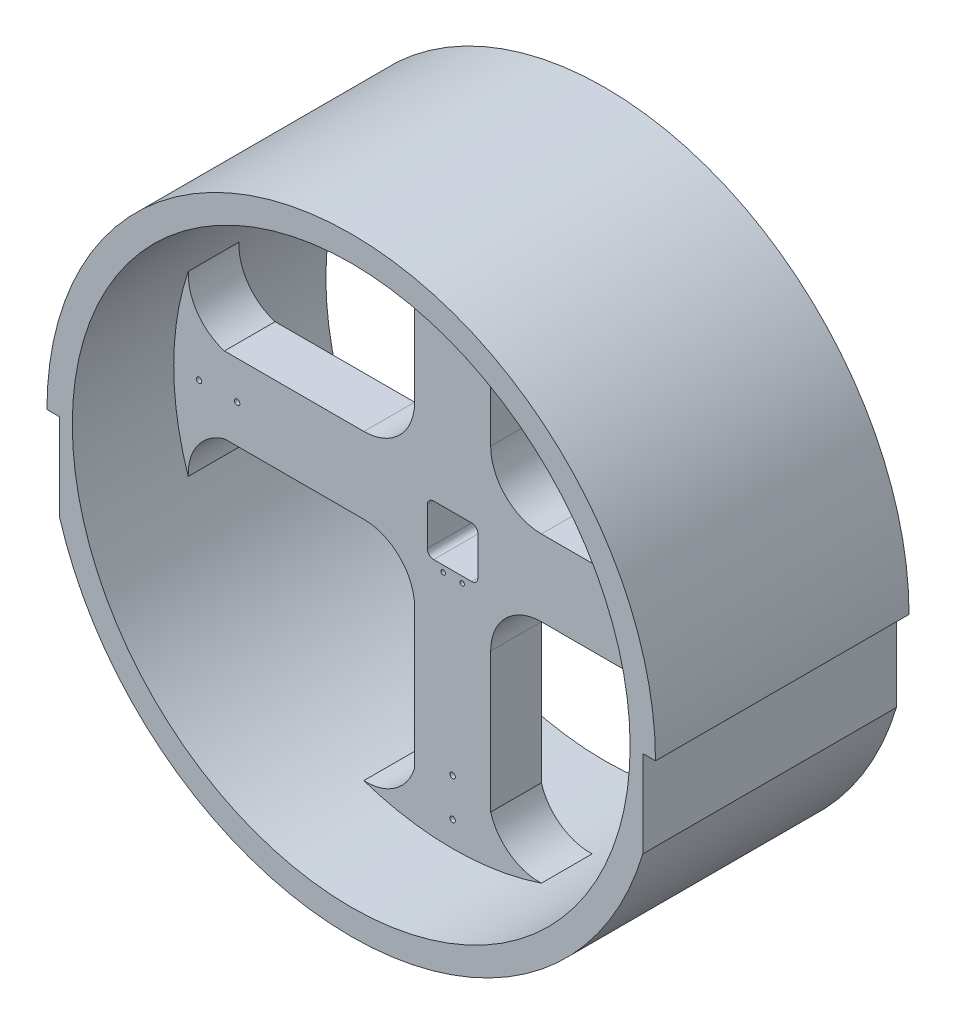
SolidWorks part; units mm, degrees
material "6061 Alloy"
ref_plane "Front Plane" through (0, 0, 0) normal (0, 0, 1) x (1, 0, 0)
ref_plane "Top Plane" through (0, 0, 0) normal (0, 1, 0) x (1, 0, 0)
ref_plane "Right Plane" through (0, 0, 0) normal (1, 0, 0) x (0, 0, -1)
sketch "Sketch1" plane through (0, 0, 0) normal (0, 0, 1) x (1, 0, 0)
  circle A0 centre (0, 0) radius 152.4
  circle A1 centre (0, 0) radius 139.7
  dimension "D1" = 304.8
  dimension "D2" = 279.4
extrude "Boss-Extrude1" add sketch "Sketch1" along normal mid plane 127
sketch "Sketch2" plane through (0, 0, 0) normal (0, 0, 1) x (1, 0, 0)
  line L0 (-114.3, 19.05) -> (-138.7192, 19.05)
  line L1 (-147.1918, -19.05) -> (147.1918, -19.05)
  line L2 (-147.1918, -19.05) -> (-147.1918, 19.05)
  line L3 (-147.1918, 19.05) -> (147.1918, 19.05)
  line L4 (147.1918, -19.05) -> (147.1918, 19.05)
  line L5 (-147.1918, -19.05) -> (147.1918, 19.05) construction
  line L6 (-147.1918, 19.05) -> (147.1918, -19.05) construction
  line L7 (19.05, -143.9568) -> (-19.05, -143.9568)
  line L8 (19.05, -143.9568) -> (19.05, 143.9568)
  line L9 (19.05, 143.9568) -> (-19.05, 143.9568)
  line L10 (-19.05, -143.9568) -> (-19.05, 143.9568)
  line L11 (19.05, -143.9568) -> (-19.05, 143.9568) construction
  line L12 (19.05, 143.9568) -> (-19.05, -143.9568) construction
  line L15 (-44.45, 19.05) -> (-19.05, 19.05)
  line L16 (-19.05, 44.45) -> (-19.05, 19.05)
  line L17 (-132.4254, 44.4927) -> (-143.3503, 19.05)
  line L18 (-143.3503, 19.05) -> (-138.7192, 19.05)
  line L19 (-138.7192, 19.05) -> (-143.3503, 19.05)
  line L20 (-19.05, 114.3) -> (-19.05, 143.9568)
  line L21 (-44.45, 132.4398) -> (-19.05, 143.9568)
  line L22 (44.45, 19.05) -> (19.05, 19.05)
  line L23 (19.05, 44.45) -> (19.05, 19.05)
  line L24 (19.05, 143.3503) -> (19.05, 138.7192)
  line L25 (19.05, 114.3) -> (19.05, 138.7192)
  line L26 (44.4927, 132.4254) -> (19.05, 143.3503)
  line L27 (114.3, 19.05) -> (143.9568, 19.05)
  line L28 (132.4398, 44.45) -> (143.9568, 19.05)
  line L29 (19.05, -44.45) -> (19.05, -19.05)
  line L30 (44.45, -19.05) -> (19.05, -19.05)
  line L31 (143.3503, -19.05) -> (138.7192, -19.05)
  line L32 (114.3, -19.05) -> (138.7192, -19.05)
  line L33 (132.4254, -44.4927) -> (143.3503, -19.05)
  line L34 (19.05, -114.3) -> (19.05, -143.9568)
  line L35 (44.45, -132.4398) -> (19.05, -143.9568)
  line L36 (-44.45, -19.05) -> (-19.05, -19.05)
  line L37 (-19.05, -44.45) -> (-19.05, -19.05)
  line L38 (-19.05, -143.3503) -> (-19.05, -138.7192)
  line L39 (-19.05, -114.3) -> (-19.05, -138.7192)
  line L40 (-44.4927, -132.4254) -> (-19.05, -143.3503)
  line L41 (-114.3, -19.05) -> (-143.9568, -19.05)
  line L42 (-132.4398, -44.45) -> (-143.9568, -19.05)
  arc A1 (-44.45, 19.05) -> (-19.05, 44.45) centre (-44.45, 44.45) ccw
  arc A2 (-114.3, 19.05) -> (-132.4254, 44.4927) centre (-107.0492, 43.3931) cw
  circle A3 centre (0, 0) radius 139.7 construction
  arc A5 (-19.05, 114.3) -> (-44.45, 132.4398) centre (-43.3968, 107.0616) ccw
  arc A6 (19.05, 44.45) -> (44.45, 19.05) centre (44.45, 44.45) ccw
  arc A7 (19.05, 114.3) -> (44.4927, 132.4254) centre (43.3931, 107.0492) cw
  arc A8 (114.3, 19.05) -> (132.4398, 44.45) centre (107.0616, 43.3968) ccw
  arc A9 (44.45, -19.05) -> (19.05, -44.45) centre (44.45, -44.45) ccw
  arc A10 (114.3, -19.05) -> (132.4254, -44.4927) centre (107.0492, -43.3931) cw
  arc A11 (19.05, -114.3) -> (44.45, -132.4398) centre (43.3968, -107.0616) ccw
  arc A12 (-19.05, -44.45) -> (-44.45, -19.05) centre (-44.45, -44.45) ccw
  arc A13 (-19.05, -114.3) -> (-44.4927, -132.4254) centre (-43.3931, -107.0492) cw
  arc A14 (-114.3, -19.05) -> (-132.4398, -44.45) centre (-107.0616, -43.3968) ccw
  point P0 (0, 0)
  point P6 (0, 0)
  point P67 (0, 0)
  dimension "D3" = 25.4
  dimension "D5" = 25.4
  dimension "D1" = 38.1
  dimension "D2" = 38.1
  dimension "D4" = 114.3
  dimension "D6" = 114.3
  dimension "D7" = 4
extrude "Boss-Extrude2" add sketch "Sketch2" along normal mid plane 25.4 contours L1 L10 L3 L2 | L10 L1 L8 L3 | L10 L3 L8 L9 | L8 L1 L4 L3 | L10 L7 L8 L1 | A14 L1 L42 | L10 A13 L40 | A11 L8 L35 | A9 L1 L8 | L1 A10 L33 | A8 L3 L28 | L8 A7 L26 | A5 L10 L21 | L0 A2 L17 L3 | A1 L3 L10 | A6 L8 L3 | A12 L10 L1 region at (-83.1209, 0, 0) region at (-132.2215, 26.1932, 0) region at (-24.7235, 24.7235, 0) region at (0, 81.5034, 0) region at (0, 0, 0) region at (24.7235, 24.7235, 0) region at (83.1209, 0, 0) region at (-24.7235, -24.7235, 0) region at (0, -81.5034, 0) region at (-26.2233, 132.4495, 0) region at (24.7235, -24.7235, 0) region at (-132.4495, -26.2233, 0) region at (132.4495, 26.2233, 0) region at (26.1932, 132.2215, 0) region at (-26.1932, -132.2215, 0) region at (132.2215, -26.1932, 0) region at (26.2233, -132.4495, 0)
sketch "Sketch4" plane through (0, 0, 0) normal (0, 0, 1) x (1, 0, 0)
  line L0 (-12.7, -19.05) -> (-12.7, 6.35)
  line L5 (-12.7, -19.05) -> (12.7, -19.05)
  line L6 (-12.7, 6.35) -> (12.7, 6.35)
  line L7 (12.7, -19.05) -> (12.7, 6.35)
  line L8 (-12.7, -19.05) -> (12.7, 6.35) construction
  line L9 (-12.7, 6.35) -> (12.7, -19.05) construction
  point P0 (-5.6792, -9.9337)
  point P1 (0, -6.35)
  dimension "D1" = 25.4
  dimension "D2" = 25.4
  dimension "D3" = 0
  dimension "D4" = 6.35
extrude "Cut-Extrude3" cut sketch "Sketch4" against normal through all both and the other way through all
sketch "Sketch8" plane through (0, 0, 63.5) normal (0, 0, 1) x (1, 0, 0)
  line L0 (-146.05, 0) -> (-163.2527, 0)
  line L1 (-146.05, 0) -> (-146.05, -50.8)
  line L2 (-163.2527, 0) -> (-163.2527, -50.8)
  line L3 (-146.05, -50.8) -> (-163.2527, -50.8)
  circle A0 centre (0, 0) radius 152.4 construction
  dimension "D1" = 50.8
  dimension "D2" = 146.05
extrude "Cut-Extrude5" cut sketch "Sketch8" against normal through all
mirror "Mirror1" about plane through (0, 0, 0) normal (1, 0, 0) of "Cut-Extrude5"
hole_wizard "#4-40 Tapped Hole1" positions "Sketch11" profile "Sketch12" tap size "#4-40" standard "ANSI Inch" end condition through all
sketch "Sketch11" plane through (0, 0, 12.7) normal (0, 0, 1) x (1, 0, 0)
  line L0 (-19.05, 44.45) -> (-19.05, 114.3) construction
  line L1 (44.45, 19.05) -> (114.3, 19.05) construction
  point P0 (-14.2875, 88.9)
  point P2 (-6.0325, 88.9)
  point P4 (88.9, 14.2875)
  point P6 (88.9, 6.0325)
  dimension "D1" = 88.9
  dimension "D2" = 88.9
  dimension "D3" = 8.255
  dimension "D4" = 8.255
  dimension "D5" = 88.9
  dimension "D6" = 4.7625
  dimension "D7" = 4.7625
sketch "Sketch12" plane through (-14.2875, 88.9, 12.7) normal (1, 0, 0) x (0, -1, 0)
  line L0 (0, 0) -> (0, 76.2)
  line L1 (0, 76.2) -> (1.1303, 76.2)
  line L2 (1.1303, 76.2) -> (1.1303, 0)
  line L5 (1.1303, 0) -> (0, 0)
  line L11 (0, -6.35) -> (0, 107.95) construction
  dimension "Thru Tap Drill Dia." = 2.2606
  dimension "Thru Tap Drill Depth" = 76.2
cosmetic thread "Hole Thread1" parameters "D2"=2.8448
cosmetic thread "Hole Thread2" parameters "D2"=2.8448
cosmetic thread "Hole Thread3" parameters "D2"=2.8448
cosmetic thread "Hole Thread4" parameters "D2"=2.8448
hole_wizard "#6-32 Tapped Hole1" positions "Sketch13" profile "Sketch14" tap size "#6-32" standard "ANSI Inch" end condition through all
sketch "Sketch13" plane through (0, 0, 12.7) normal (0, 0, 1) x (1, 0, 0)
  point P0 (-107.95, 0)
  point P2 (-127, 0)
  dimension "D1" = 107.95
  dimension "D2" = 19.05
sketch "Sketch14" plane through (-107.95, 0, 12.7) normal (1, 0, 0) x (0, -1, 0)
  line L0 (0, 0) -> (0, 76.2)
  line L1 (0, 76.2) -> (1.3525, 76.2)
  line L2 (1.3525, 76.2) -> (1.3525, 0)
  line L5 (1.3525, 0) -> (0, 0)
  line L11 (0, -6.35) -> (0, 107.95) construction
  dimension "Thru Tap Drill Dia." = 2.7051
  dimension "Thru Tap Drill Depth" = 76.2
cosmetic thread "Hole Thread5" parameters "D2"=3.5052
cosmetic thread "Hole Thread6" parameters "D2"=3.5052
pattern_circular "CirPattern1" count 4 every 90 about axis through (0, 0, 63.5) along (0, 0, 1) of "#6-32 Tapped Hole1"
hole_wizard "#4-40 Tapped Hole2" positions "Sketch15" profile "Sketch16" tap size "#4-40" standard "ANSI Inch" end condition up to next
sketch "Sketch15" plane through (0, 0, 12.7) normal (0, 0, 1) x (1, 0, 0)
  line L0 (-12.7, -19.05) -> (12.7, -19.05) construction
  point P0 (-4.7625, -22.225)
  point P2 (4.7625, -22.225)
  point P9 (-4.951, -22.2177)
  dimension "D1" = 9.525
  dimension "D2" = 4.7625
  dimension "D3" = 3.175
sketch "Sketch16" plane through (-4.7625, -22.225, 12.7) normal (1, 0, 0) x (0, -1, 0)
  line L0 (0, 0) -> (0, 25.4)
  line L1 (0, 25.4) -> (1.1303, 25.4)
  line L2 (1.1303, 25.4) -> (1.1303, 0)
  line L5 (1.1303, 0) -> (0, 0)
  line L11 (0, -6.35) -> (0, 107.95) construction
  dimension "Thru Tap Drill Dia." = 2.2606
  dimension "Thru Tap Drill Depth" = 25.4
cosmetic thread "Hole Thread7" parameters "D2"=2.8448
cosmetic thread "Hole Thread8" parameters "D2"=2.8448
sketch "Sketch17" plane through (0, 0, 12.7) normal (0, 0, 1) x (1, 0, 0)
  line L0 (-12.7, -19.05) -> (12.7, -19.05) construction
  line L1 (-12.7, 6.35) -> (-12.7, -19.05) construction
  line L2 (-12.7, -15.875) -> (-12.7, -19.05)
  line L3 (-12.7, -19.05) -> (-9.525, -19.05)
  line L4 (12.7, 6.35) -> (-12.7, 6.35) construction
  line L5 (12.7, -19.05) -> (12.7, 6.35) construction
  line L6 (-12.7, 3.175) -> (-12.7, 6.35)
  line L7 (-12.7, 6.35) -> (-9.525, 6.35)
  line L8 (9.525, 6.35) -> (12.7, 6.35)
  line L9 (12.7, 6.35) -> (12.7, 3.175)
  line L10 (12.7, -15.875) -> (12.7, -19.05)
  line L11 (12.7, -19.05) -> (9.525, -19.05)
  arc A0 (-9.525, -19.05) -> (-12.7, -15.875) centre (-9.525, -15.875) cw
  arc A1 (-12.7, 3.175) -> (-9.525, 6.35) centre (-9.525, 3.175) cw
  arc A2 (9.525, 6.35) -> (12.7, 3.175) centre (9.525, 3.175) cw
  arc A3 (9.525, -19.05) -> (12.7, -15.875) centre (9.525, -15.875) ccw
  dimension "D1" = 3.175
  dimension "D4" = 3.175
  dimension "D5" = 3.175
  dimension "D6" = 3.175
  dimension "D12" = 3.175
  dimension "D2" = 3.175
  dimension "D3" = 3.175
  dimension "D7" = 3.175
  dimension "D8" = 3.175
  dimension "D9" = 3.175
  dimension "D10" = 3.175
  dimension "D11" = 3.175
extrude "Boss-Extrude4" add sketch "Sketch17" against normal up to surface (25.4 mm away) up to face at (-3.6322, -22.225, -12.7)
